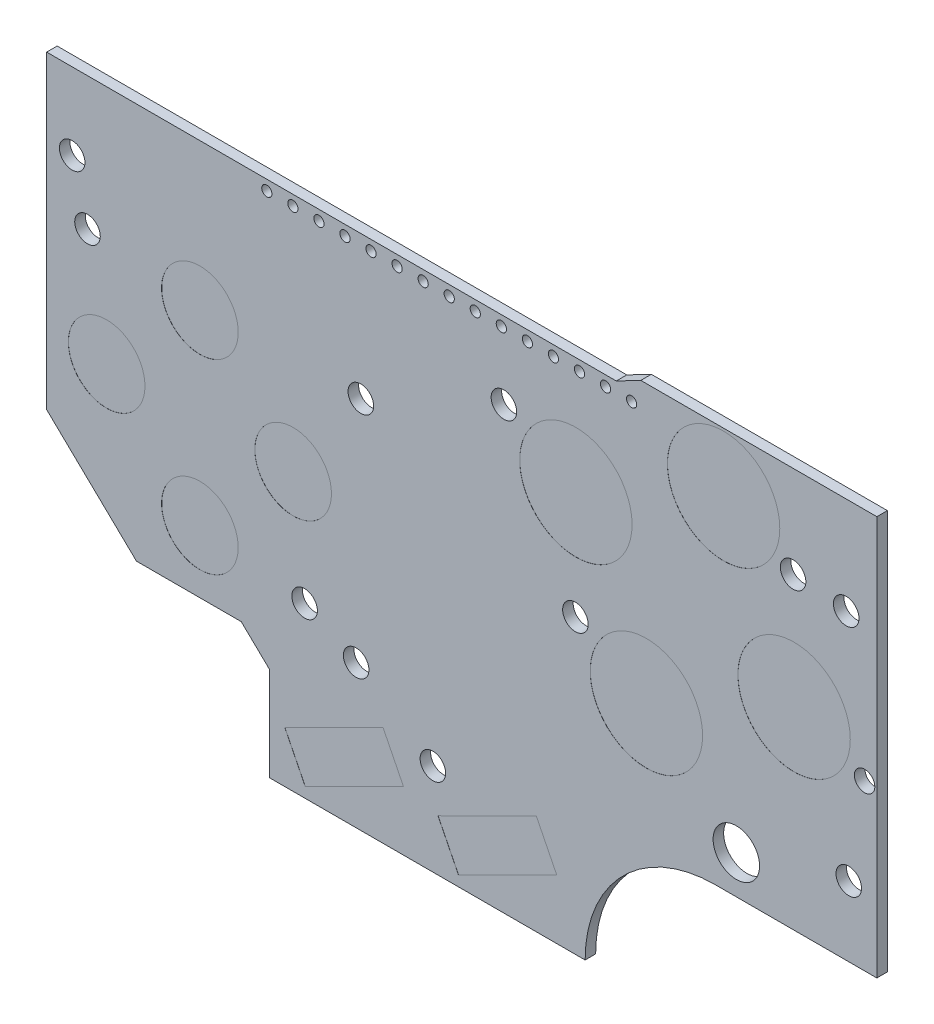
SolidWorks part; units mm, degrees
ref_plane "Front Plane" through (0, 0, 0) normal (0, 0, 1) x (1, 0, 0)
ref_plane "Top Plane" through (0, 0, 0) normal (0, 1, 0) x (1, 0, 0)
ref_plane "Right Plane" through (0, 0, 0) normal (1, 0, 0) x (0, 0, -1)
sketch "Sketch1" plane through (0, 0, 0) normal (0, 0, 1) x (1, 0, 0)
  line L0 (0, 0) -> (55.75, 0)
  line L1 (55.75, 0) -> (58.15, 1.25)
  line L2 (58.15, 1.25) -> (81.25, 1.25)
  line L3 (81.25, 1.25) -> (81.25, -37.85)
  line L4 (81.25, -37.85) -> (65.45, -37.85)
  line L5 (0, 0) -> (0, -30.3)
  line L6 (0, -30.3) -> (8.7926, -38.75)
  line L7 (8.7926, -38.75) -> (19.0426, -38.75)
  line L8 (19.0426, -38.75) -> (21.8, -41.4)
  line L9 (21.8, -41.4) -> (21.8, -50.6)
  line L10 (21.8, -50.6) -> (52.7, -50.6)
  arc A0 (65.45, -37.85) -> (52.7, -50.6) centre (65.45, -50.6) ccw
  dimension "D1" = 39.1
  dimension "D2" = 38.75
  dimension "D3" = 50.6
  dimension "D4" = 30.9
  dimension "D5" = 81.25
  dimension "D6" = 25.5
  dimension "D7" = 23.1
  dimension "D8" = 1.25
  dimension "D9" = 21.8
  dimension "D10" = 10.25
  dimension "D11" = 30.3
  dimension "D12" = 9.2
extrude "Boss-Extrude1" add sketch "Sketch1" along normal mid plane 1.03
sketch "Sketch6" plane through (0, 0, 0.515) normal (0, 0, 1) x (1, 0, 0)
  line L0 (81.25, -37.85) -> (81.25, 1.25) construction
  line L1 (55.75, 0) -> (0, 0) construction
  circle A0 centre (57.25, -1) radius 0.5
  dimension "D1" = 1
  dimension "D2" = 24
  dimension "D3" = 1
extrude "Cut-Extrude1" cut sketch "Sketch6" against normal through all
pattern_linear "LPattern1" count 15 spacing 2.55 along (-1, 0, 0) of "Cut-Extrude1"
sketch "Sketch5" plane through (0, 0, 0.515) normal (0, 0, 1) x (1, 0, 0)
  line L0 (32.9189, -40.7735) -> (23.3, -45.5735)
  line L1 (32.9189, -40.7735) -> (34.9282, -44.8)
  line L2 (23.3, -45.5735) -> (25.3093, -49.6)
  line L3 (34.9282, -44.8) -> (25.3093, -49.6)
  line L4 (38.3, -45.5735) -> (40.3093, -49.6)
  line L5 (38.3, -45.5735) -> (47.9189, -40.7735)
  line L6 (40.3093, -49.6) -> (49.9282, -44.8)
  line L7 (47.9189, -40.7735) -> (49.9282, -44.8)
  line L8 (21.8, -41.4) -> (21.8, -50.6) construction
  line L9 (21.8, -50.6) -> (52.7, -50.6) construction
  dimension "D1" = 10.75
  dimension "D2" = 4.5
  dimension "D3" = 1.5
  dimension "D4" = 1
  dimension "D5" = 16.5
  dimension "D6" = 5.8
extrude "Cut-Extrude17" cut sketch "Sketch5" against normal blind 0.01
sketch "Sketch2" plane through (0, 0, 0.515) normal (0, 0, 1) x (1, 0, 0)
  line L0 (66.25, -4.5) -> (51.7962, -11.4086) construction
  line L1 (66.25, -4.5) -> (73.15, -18.9357) construction
  line L2 (51.7962, -11.4086) -> (58.6962, -25.8443) construction
  line L3 (73.15, -18.9357) -> (58.6962, -25.8443) construction
  line L4 (81.25, -37.85) -> (81.25, 1.25) construction
  line L8 (81.25, 1.25) -> (58.15, 1.25) construction
  circle A0 centre (66.25, -4.5) radius 5.5
  circle A1 centre (73.15, -18.9357) radius 5.5
  circle A2 centre (58.6962, -25.8443) radius 5.5
  circle A3 centre (51.7962, -11.4086) radius 5.5
  dimension "D1" = 16.02
  dimension "D3" = 11
  dimension "D2" = 16
  dimension "D4" = 8.1
  dimension "D5" = 15
  dimension "D6" = 5.75
extrude "Cut-Extrude14" cut sketch "Sketch2" against normal blind 0.01
sketch "Sketch3" plane through (0, 0, 0.515) normal (0, 0, 1) x (1, 0, 0)
  line L9 (15, -14.375) -> (15, -32.625) construction
  line L10 (24.125, -23.5) -> (5.875, -23.5) construction
  circle A4 centre (15, -14.375) radius 3.75
  circle A5 centre (15, -32.625) radius 3.75
  circle A6 centre (24.125, -23.5) radius 3.75
  circle A7 centre (5.875, -23.5) radius 3.75
  point P23 (15, -23.5)
  point P24 (15, -23.5)
  dimension "D3" = 14.375
  dimension "D10" = 7.5
  dimension "D2" = 5.875
  dimension "D9" = 18.25
extrude "Cut-Extrude16" cut sketch "Sketch3" against normal blind 0.01
sketch "Sketch8" plane through (0, 0, 0.515) normal (0, 0, 1) x (1, 0, 0)
  line L0 (81.25, -37.85) -> (81.25, 1.25) construction
  line L1 (81.25, 1.25) -> (58.15, 1.25) construction
  circle A0 centre (78.25, -8.25) radius 1.25
  dimension "D1" = 2.5
  dimension "D2" = 3
  dimension "D3" = 9.5
extrude "Cut-Extrude3" cut sketch "Sketch8" against normal through all
sketch "Sketch9" plane through (0, 0, 0.515) normal (0, 0, 1) x (1, 0, 0)
  line L0 (81.25, -37.85) -> (81.25, 1.25) construction
  line L1 (81.25, 1.25) -> (58.15, 1.25) construction
  circle A0 centre (73.05, -7.75) radius 1.25
  dimension "D1" = 2.5
  dimension "D2" = 8.2
  dimension "D3" = 9
extrude "Cut-Extrude4" cut sketch "Sketch9" against normal through all
sketch "Sketch10" plane through (0, 0, 0.515) normal (0, 0, 1) x (1, 0, 0)
  line L0 (81.25, -37.85) -> (81.25, 1.25) construction
  line L1 (55.75, 0) -> (0, 0) construction
  circle A0 centre (44.75, -7.5) radius 1.25
  dimension "D1" = 2.5
  dimension "D2" = 36.5
  dimension "D3" = 7.5
extrude "Cut-Extrude5" cut sketch "Sketch10" against normal through all
sketch "Sketch11" plane through (0, 0, 0.515) normal (0, 0, 1) x (1, 0, 0)
  line L0 (81.25, -37.85) -> (81.25, 1.25) construction
  line L1 (55.75, 0) -> (0, 0) construction
  circle A0 centre (51.75, -22) radius 1.25
  dimension "D1" = 2.5
  dimension "D2" = 29.5
  dimension "D3" = 22
extrude "Cut-Extrude6" cut sketch "Sketch11" against normal through all
sketch "Sketch12" plane through (0, 0, 0.515) normal (0, 0, 1) x (1, 0, 0)
  line L0 (21.8, -50.6) -> (52.7, -50.6) construction
  line L1 (21.8, -41.4) -> (21.8, -50.6) construction
  circle A0 centre (37.8, -41.6) radius 1.25
  dimension "D1" = 2.5
  dimension "D2" = 9
  dimension "D3" = 16
extrude "Cut-Extrude7" cut sketch "Sketch12" against normal through all
sketch "Sketch13" plane through (0, 0, 0.515) normal (0, 0, 1) x (1, 0, 0)
  line L1 (21.8, -50.6) -> (52.7, -50.6) construction
  circle A0 centre (30.2926, -36.6) radius 1.25
  dimension "D1" = 21.5
  dimension "D3" = 2.5
  dimension "D2" = 14
extrude "Cut-Extrude8" cut sketch "Sketch13" against normal through all
sketch "Sketch14" plane through (0, 0, 0.515) normal (0, 0, 1) x (1, 0, 0)
  line L0 (81.25, -37.85) -> (81.25, 1.25) construction
  line L1 (21.8, -50.6) -> (52.7, -50.6) construction
  circle A0 centre (25.25, -34.1) radius 1.25
  dimension "D1" = 2.5
  dimension "D2" = 56
  dimension "D3" = 16.5
extrude "Cut-Extrude9" cut sketch "Sketch14" against normal through all
sketch "Sketch15" plane through (0, 0, 0.515) normal (0, 0, 1) x (1, 0, 0)
  line L0 (81.25, -37.85) -> (81.25, 1.25) construction
  line L1 (55.75, 0) -> (0, 0) construction
  circle A0 centre (30.75, -14) radius 1.25
  dimension "D1" = 2.5
  dimension "D2" = 50.5
  dimension "D3" = 14
extrude "Cut-Extrude10" cut sketch "Sketch15" against normal through all
sketch "Sketch16" plane through (0, 0, 0.515) normal (0, 0, 1) x (1, 0, 0)
  line L0 (55.75, 0) -> (0, 0) construction
  line L1 (0, 0) -> (0, -30.3) construction
  circle A0 centre (2.5, -7.5) radius 1.25
  dimension "D1" = 2.5
  dimension "D2" = 7.5
  dimension "D3" = 2.5
extrude "Cut-Extrude11" cut sketch "Sketch16" against normal through all
sketch "Sketch17" plane through (0, 0, 0.515) normal (0, 0, 1) x (1, 0, 0)
  line L0 (55.75, 0) -> (0, 0) construction
  line L1 (0, 0) -> (0, -30.3) construction
  circle A0 centre (4, -13) radius 1.25
  dimension "D1" = 2.5
  dimension "D2" = 13
  dimension "D3" = 4
extrude "Cut-Extrude12" cut sketch "Sketch17" against normal through all
sketch "Sketch7" plane through (0, 0, 0.515) normal (0, 0, 1) x (1, 0, 0)
  line L0 (65.45, -37.85) -> (81.25, -37.85) construction
  line L1 (81.25, -37.85) -> (81.25, 1.25) construction
  circle A0 centre (67.5, -34.1) radius 2.275
  circle A1 centre (78.5, -31) radius 1.25
  dimension "D1" = 4.55
  dimension "D4" = 2.5
  dimension "D2" = 3.75
  dimension "D3" = 13.75
  dimension "D5" = 2.75
  dimension "D6" = 6.85
extrude "Cut-Extrude2" cut sketch "Sketch7" against normal through all
sketch "Sketch18" plane through (0, 0, 0.515) normal (0, 0, 1) x (1, 0, 0)
  line L0 (81.25, -37.85) -> (81.25, 1.25) construction
  line L1 (81.25, 1.25) -> (58.15, 1.25) construction
  circle A0 centre (80.05, -21.75) radius 1
  dimension "D1" = 2
  dimension "D2" = 1.2
  dimension "D3" = 23
extrude "Cut-Extrude13" cut sketch "Sketch18" against normal through all
